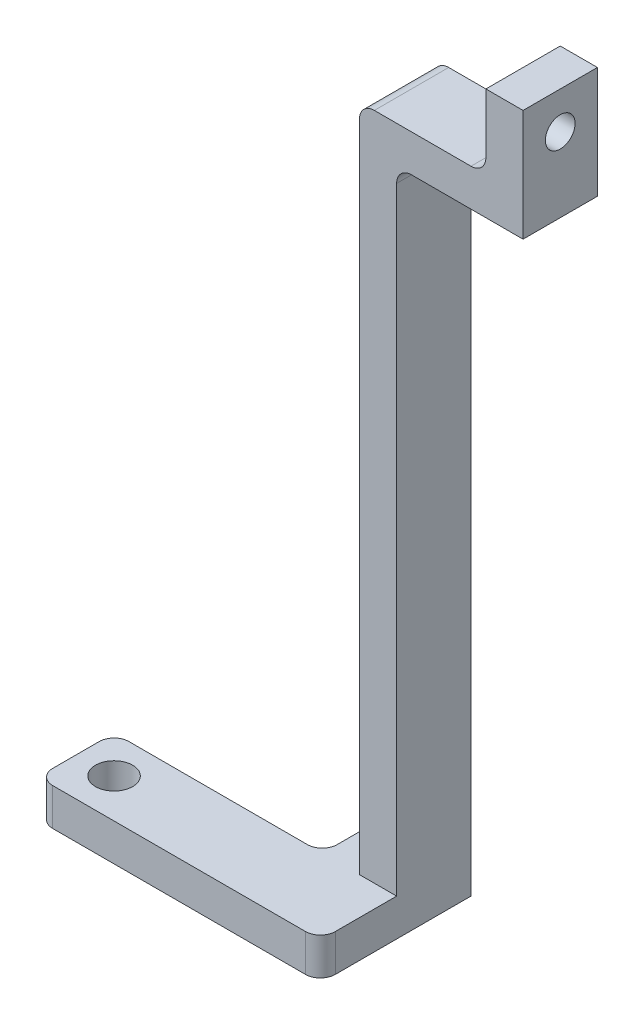
SolidWorks part; units mm, degrees
ref_plane "Front Plane" through (0, 0, 0) normal (0, 0, 1) x (1, 0, 0)
ref_plane "Top Plane" through (0, 0, 0) normal (0, 1, 0) x (1, 0, 0)
ref_plane "Right Plane" through (0, 0, 0) normal (1, 0, 0) x (0, 0, -1)
sketch "Sketch1" plane through (0, 0, 0) normal (0, 1, 0) x (1, 0, 0)
  line L0 (-8, 56.9408) -> (-8, 59.7408)
  line L1 (0, 57.5) -> (0, -57.5) construction
  line L2 (8, 56.9408) -> (8, 59.7408)
  line L3 (-6, 61.7408) -> (6, 61.7408)
  line L4 (39.4147, 47.8999) -> (47.8999, 39.4147)
  line L9 (34.6063, 45.9201) -> (36.5862, 47.8999)
  line L10 (45.9201, 34.6063) -> (47.8999, 36.5862)
  line L15 (61.7408, 6) -> (61.7408, -6)
  line L16 (56.9408, 8) -> (59.7408, 8)
  line L17 (56.9408, -8) -> (59.7408, -8)
  line L22 (47.8999, -39.4147) -> (39.4147, -47.8999)
  line L23 (45.9201, -34.6063) -> (47.8999, -36.5862)
  line L24 (34.6063, -45.9201) -> (36.5862, -47.8999)
  line L29 (6, -61.7408) -> (-6, -61.7408)
  line L30 (8, -56.9408) -> (8, -59.7408)
  line L31 (-8, -56.9408) -> (-8, -59.7408)
  line L36 (-39.4147, -47.8999) -> (-47.8999, -39.4147)
  line L37 (-34.6063, -45.9201) -> (-36.5862, -47.8999)
  line L38 (-45.9201, -34.6063) -> (-47.8999, -36.5862)
  line L43 (-61.7408, -6) -> (-61.7408, 6)
  line L44 (-56.9408, -8) -> (-59.7408, -8)
  line L45 (-56.9408, 8) -> (-59.7408, 8)
  line L50 (-47.8999, 39.4147) -> (-39.4147, 47.8999)
  line L51 (-45.9201, 34.6063) -> (-47.8999, 36.5862)
  line L52 (-34.6063, 45.9201) -> (-36.5862, 47.8999)
  arc A0 (-8, 56.9408) -> (-34.6063, 45.9201) centre (0, 0) ccw
  arc A1 (6, 61.7408) -> (8, 59.7408) centre (6, 59.7408) cw
  arc A2 (-6, 61.7408) -> (-8, 59.7408) centre (-6, 59.7408) ccw
  arc A3 (39.4147, 47.8999) -> (36.5862, 47.8999) centre (38.0005, 46.4857) ccw
  arc A4 (47.8999, 39.4147) -> (47.8999, 36.5862) centre (46.4857, 38.0005) cw
  arc A5 (61.7408, 6) -> (59.7408, 8) centre (59.7408, 6) ccw
  arc A6 (61.7408, -6) -> (59.7408, -8) centre (59.7408, -6) cw
  arc A7 (47.8999, -39.4147) -> (47.8999, -36.5862) centre (46.4857, -38.0005) ccw
  arc A8 (39.4147, -47.8999) -> (36.5862, -47.8999) centre (38.0005, -46.4857) cw
  arc A9 (6, -61.7408) -> (8, -59.7408) centre (6, -59.7408) ccw
  arc A10 (-6, -61.7408) -> (-8, -59.7408) centre (-6, -59.7408) cw
  arc A11 (-39.4147, -47.8999) -> (-36.5862, -47.8999) centre (-38.0005, -46.4857) ccw
  arc A12 (-47.8999, -39.4147) -> (-47.8999, -36.5862) centre (-46.4857, -38.0005) cw
  arc A13 (-61.7408, -6) -> (-59.7408, -8) centre (-59.7408, -6) ccw
  arc A14 (-61.7408, 6) -> (-59.7408, 8) centre (-59.7408, 6) cw
  arc A15 (-47.8999, 39.4147) -> (-47.8999, 36.5862) centre (-46.4857, 38.0005) ccw
  arc A16 (-39.4147, 47.8999) -> (-36.5862, 47.8999) centre (-38.0005, 46.4857) cw
  arc A17 (-45.9201, 34.6063) -> (-56.9408, 8) centre (0, 0) ccw
  arc A18 (-56.9408, -8) -> (-45.9201, -34.6063) centre (0, 0) ccw
  arc A19 (34.6063, 45.9201) -> (8, 56.9408) centre (0, 0) ccw
  arc A20 (-34.6063, -45.9201) -> (-8, -56.9408) centre (0, 0) ccw
  arc A21 (8, -56.9408) -> (34.6063, -45.9201) centre (0, 0) ccw
  arc A22 (45.9201, -34.6063) -> (56.9408, -8) centre (0, 0) ccw
  arc A23 (56.9408, 8) -> (45.9201, 34.6063) centre (0, 0) ccw
  point P11 (8, 61.7408)
  point P14 (-8, 61.7408)
  point P17 (-8, 58.3408)
  point P98 (0, 0)
  dimension "D1" = 115
  dimension "D2" = 2
  dimension "D3" = 16
  dimension "D4" = 2.8
  dimension "D7" = 8
extrude "Boss-Extrude1" add sketch "Sketch1" along normal blind 7
sketch "Sketch2" plane through (0, 7, 0) normal (0, 1, 0) x (1, 0, 0)
  line L0 (-57.5, 0) -> (57.5, 0) construction
  line L1 (0, 0) -> (0, 10) construction
  line L7 (17, 5) -> (22, 5)
  line L14 (0, 10) -> (29.7122, 10) construction
  line L15 (0, 10) -> (-19.5, 10) construction
  line L17 (17, 5) -> (17, 15)
  line L18 (-22, 15) -> (-17, 15)
  line L19 (-22, 15) -> (-22, 5)
  line L20 (-22, 5) -> (-17, 5)
  line L21 (-17, 15) -> (-17, 5)
  line L22 (-22, 15) -> (-17, 5) construction
  line L23 (-22, 5) -> (-17, 15) construction
  line L24 (17, 15) -> (22, 15)
  line L25 (22, 5) -> (22, 15)
  line L26 (17, 5) -> (22, 15) construction
  line L27 (17, 15) -> (22, 5) construction
  circle A0 centre (0, 0) radius 57.5 construction
  point P8 (19.5, 10)
  dimension "D1" = 10
  dimension "D2" = 17
  dimension "D3" = 17
  dimension "D4" = 10
  dimension "D5" = 5
  dimension "D6" = 10
  dimension "D7" = 5
extrude "Boss-Extrude2" add sketch "Sketch2" along normal blind 95
sketch "Sketch15" plane through (0, 0, 0) normal (0, -1, 0) x (1, 0, 0)
  circle A0 centre (0, 0) radius 3.5
  dimension "D1" = 7
extrude "Cut-Extrude3" cut sketch "Sketch15" along direction (0, 1, 0) on the side against the normal up to surface (7 mm away) contours A0 up to face at (0, 7, 0)
sketch "Sketch16" plane through (0, 0, 0) normal (0, -1, 0) x (1, 0, 0)
  line L1 (-6, 59.8) -> (6, 59.8)
  line L2 (-6, 59.8) -> (-6, 57.5)
  line L3 (-6, 57.5) -> (6, 57.5)
  line L4 (6, 59.8) -> (6, 57.5)
  point P5 (0, 57.5)
  dimension "D1" = 2.3
  dimension "D2" = 12
  dimension "D3" = 57.5
sketch "Sketch17" plane through (0, 7, 0) normal (0, 1, 0) x (1, 0, 0)
  line L0 (-6, -57.5) -> (6, -57.5) construction
  line L1 (-6, -57.5) -> (6, -57.5)
  line L2 (-6, -57.5) -> (-6, -60.5)
  line L3 (-6, -60.5) -> (6, -60.5)
  line L4 (6, -60.5) -> (6, -57.5)
  dimension "D1" = 3
ref_axis "Axis1" through (0, 107.1, 0) along (0, -1, 0)
loft "Cut-Loft2" cut profiles "Sketch16", "Sketch17" connector at (6, 0, 59.8) connector at (6, 7, 60.5)
pattern_circular "CirPattern1" count 8 over 360 about axis through (0, 107.1, 0) along (0, -1, 0) of "Cut-Loft2"
sketch "Sketch18" plane through (-17, 0, 0) normal (1, 0, 0) x (0, 0, -1)
  line L0 (15, 102) -> (15, 7) construction
  line L1 (5, 102) -> (15, 102)
  line L2 (5, 102) -> (5, 97)
  line L3 (5, 97) -> (15, 97)
  line L4 (15, 102) -> (15, 97)
  dimension "D1" = 5
extrude "Boss-Extrude3" add sketch "Sketch18" along normal up to surface (34 mm away) up to face at (17, 54.5, -10)
sketch "Sketch19" plane through (0, 0, -15) normal (0, 0, -1) x (-1, 0, 0)
  line L0 (-17, 93) -> (-11.0447, 92.2688)
  line L1 (-17, 97) -> (-17, 7) construction
  line L4 (-11, 91) -> (-19.8185, 91) construction
  line L5 (-17, 89) -> (-11.0447, 89.7312)
  line L6 (-17, 93) -> (-17, 89)
  arc A1 (-11.0447, 92.2688) -> (-11.0447, 89.7312) centre (-11.2005, 91) cw
  dimension "D1" = 6
  dimension "D4" = 4
  dimension "D2" = 7
  dimension "D3" = 4
extrude "Boss-Extrude4" add sketch "Sketch19" against normal blind 10
fillet "Fillet1" radius 2 2 edges at (17, 93, -10) (17, 89, -10)
fillet "Fillet2" radius 2 4 edges at (-22, 102, -10) (22, 102, -10) (-17, 97, -10) (17, 97, -10)
pattern_linear "LPattern2" count 10 spacing 8 along (0, -1, 0) of "Fillet1", "Boss-Extrude4"
sketch "Sketch20" plane through (0, 7, 0) normal (0, 1, 0) x (1, 0, 0)
  line L0 (0, 0) -> (0, 50) construction
  circle A0 centre (0, 50) radius 2.5
  dimension "D2" = 5
  dimension "D1" = 50
extrude "Cut-Extrude4" cut sketch "Sketch20" against normal blind 10
pattern_circular "CirPattern2" count 4 over 360 about axis through (0, 107.1, 0) along (0, -1, 0) of "Cut-Extrude4"
sketch "Sketch21" plane through (0, 0, 0) normal (1, 0, 0) x (0, 0, -1)
  line L1 (67.451, 109.7761) -> (-68.4979, 109.7761)
  line L2 (67.451, 109.7761) -> (67.451, 0)
  line L3 (67.451, 0) -> (-68.4979, 0)
  line L4 (-68.4979, 109.7761) -> (-68.4979, 0)
  dimension "D1" = 109.7761
  dimension "D2" = 135.9489
  dimension "D3" = 68.4979
extrude "Cut-Extrude5" cut sketch "Sketch21" along normal up to surface (61.7408 mm away) up to face at (61.7408, 3.5, 0)
sketch "Sketch22" plane through (0, 7, 0) normal (0, 1, 0) x (1, 0, 0)
  line L1 (-17, 5) -> (-53, 5)
  line L2 (-17, 5) -> (-17, -3.2506)
  line L3 (-19, -5.2506) -> (-53, -5.2506)
  line L4 (-55, 3) -> (-55, -3.2506)
  circle A0 centre (-50, 0) radius 2.5 construction
  circle A1 centre (-50, 0) radius 2.5
  arc A2 (-19, -5.2506) -> (-17, -3.2506) centre (-19, -3.2506) ccw
  arc A3 (-55, 3) -> (-53, 5) centre (-53, 3) cw
  arc A4 (-53, -5.2506) -> (-55, -3.2506) centre (-53, -3.2506) cw
  point P10 (-17, -5.2506)
  point P15 (-55, -5.2506)
  dimension "D3" = 2
  dimension "D1" = 38
  dimension "D2" = 10.2506
extrude "Boss-Extrude5" add sketch "Sketch22" along normal blind 5
sketch "Sketch23" plane through (0, 7, 0) normal (0, 1, 0) x (1, 0, 0)
  line L25 (0, 60.5) -> (0, 61.7408)
  line L26 (0, 61.7408) -> (-6, 61.7408)
  line L27 (-8, 59.7408) -> (-8, 56.9408)
  line L28 (-34.6063, 45.9201) -> (-36.5862, 47.8999)
  line L29 (-39.4147, 47.8999) -> (-47.8999, 39.4147)
  line L30 (-47.8999, 36.5862) -> (-45.9201, 34.6063)
  line L31 (-56.9408, 8) -> (-59.7408, 8)
  line L32 (-61.7408, 6) -> (-61.7408, -6)
  line L33 (-59.7408, -8) -> (-56.9408, -8)
  line L34 (-45.9201, -34.6063) -> (-47.8999, -36.5862)
  line L35 (-47.8999, -39.4147) -> (-39.4147, -47.8999)
  line L36 (-36.5862, -47.8999) -> (-34.6063, -45.9201)
  line L37 (-8, -56.9408) -> (-8, -59.7408)
  line L38 (-6, -61.7408) -> (0, -61.7408)
  line L39 (0, -61.7408) -> (0, -60.5)
  line L40 (0, -60.5) -> (-6, -60.5)
  line L41 (-6, -60.5) -> (-6, -57.5)
  line L42 (-6, -57.5) -> (0, -57.5)
  line L43 (0, -57.5) -> (0, -52.5)
  line L44 (0, -47.5) -> (0, -3.5)
  line L45 (0, 3.5) -> (0, 47.5)
  line L46 (0, 52.5) -> (0, 57.5)
  line L47 (0, 57.5) -> (-6, 57.5)
  line L48 (-6, 57.5) -> (-6, 60.5)
  line L49 (-6, 60.5) -> (0, 60.5)
  line L50 (0, 60.5) -> (0, 61.7408)
  line L51 (0, 61.7408) -> (-6, 61.7408)
  line L52 (-8, 59.7408) -> (-8, 56.9408)
  line L53 (-34.6063, 45.9201) -> (-36.5862, 47.8999)
  line L54 (-39.4147, 47.8999) -> (-47.8999, 39.4147)
  line L55 (-47.8999, 36.5862) -> (-45.9201, 34.6063)
  line L56 (-56.9408, 8) -> (-59.7408, 8)
  line L57 (-61.7408, 6) -> (-61.7408, -6)
  line L58 (-59.7408, -8) -> (-56.9408, -8)
  line L59 (-45.9201, -34.6063) -> (-47.8999, -36.5862)
  line L60 (-47.8999, -39.4147) -> (-39.4147, -47.8999)
  line L61 (-36.5862, -47.8999) -> (-34.6063, -45.9201)
  line L62 (-8, -56.9408) -> (-8, -59.7408)
  line L63 (-6, -61.7408) -> (0, -61.7408)
  line L64 (0, -61.7408) -> (0, -60.5)
  line L65 (0, -60.5) -> (-6, -60.5)
  line L66 (-6, -60.5) -> (-6, -57.5)
  line L67 (-6, -57.5) -> (0, -57.5)
  line L68 (0, -57.5) -> (0, -52.5)
  line L69 (0, -47.5) -> (0, -3.5)
  line L70 (0, 3.5) -> (0, 47.5)
  line L71 (0, 52.5) -> (0, 57.5)
  line L72 (0, 57.5) -> (-6, 57.5)
  line L73 (-6, 57.5) -> (-6, 60.5)
  line L74 (-6, 60.5) -> (0, 60.5)
  arc A15 (-6, 61.7408) -> (-8, 59.7408) centre (-6, 59.7408) ccw
  arc A16 (-8, 56.9408) -> (-34.6063, 45.9201) centre (0, 0) ccw
  arc A17 (-36.5862, 47.8999) -> (-39.4147, 47.8999) centre (-38.0005, 46.4857) ccw
  arc A18 (-47.8999, 39.4147) -> (-47.8999, 36.5862) centre (-46.4857, 38.0005) ccw
  arc A19 (-45.9201, 34.6063) -> (-56.9408, 8) centre (0, 0) ccw
  arc A20 (-59.7408, 8) -> (-61.7408, 6) centre (-59.7408, 6) ccw
  arc A21 (-61.7408, -6) -> (-59.7408, -8) centre (-59.7408, -6) ccw
  arc A22 (-56.9408, -8) -> (-45.9201, -34.6063) centre (0, 0) ccw
  arc A23 (-47.8999, -36.5862) -> (-47.8999, -39.4147) centre (-46.4857, -38.0005) ccw
  arc A24 (-39.4147, -47.8999) -> (-36.5862, -47.8999) centre (-38.0005, -46.4857) ccw
  arc A25 (-34.6063, -45.9201) -> (-8, -56.9408) centre (0, 0) ccw
  arc A26 (-8, -59.7408) -> (-6, -61.7408) centre (-6, -59.7408) ccw
  arc A27 (0, -47.5) -> (0, -52.5) centre (0, -50) ccw
  arc A28 (0, 3.5) -> (0, -3.5) centre (0, 0) ccw
  arc A29 (0, 52.5) -> (0, 47.5) centre (0, 50) ccw
  arc A30 (-6, 61.7408) -> (-8, 59.7408) centre (-6, 59.7408) ccw
  arc A31 (-8, 56.9408) -> (-34.6063, 45.9201) centre (0, 0) ccw
  arc A32 (-36.5862, 47.8999) -> (-39.4147, 47.8999) centre (-38.0005, 46.4857) ccw
  arc A33 (-47.8999, 39.4147) -> (-47.8999, 36.5862) centre (-46.4857, 38.0005) ccw
  arc A34 (-45.9201, 34.6063) -> (-56.9408, 8) centre (0, 0) ccw
  arc A35 (-59.7408, 8) -> (-61.7408, 6) centre (-59.7408, 6) ccw
  arc A36 (-61.7408, -6) -> (-59.7408, -8) centre (-59.7408, -6) ccw
  arc A37 (-56.9408, -8) -> (-45.9201, -34.6063) centre (0, 0) ccw
  arc A38 (-47.8999, -36.5862) -> (-47.8999, -39.4147) centre (-46.4857, -38.0005) ccw
  arc A39 (-39.4147, -47.8999) -> (-36.5862, -47.8999) centre (-38.0005, -46.4857) ccw
  arc A40 (-34.6063, -45.9201) -> (-8, -56.9408) centre (0, 0) ccw
  arc A41 (-8, -59.7408) -> (-6, -61.7408) centre (-6, -59.7408) ccw
  arc A42 (0, -47.5) -> (0, -52.5) centre (0, -50) ccw
  arc A43 (0, 3.5) -> (0, -3.5) centre (0, 0) ccw
  arc A44 (0, 52.5) -> (0, 47.5) centre (0, 50) ccw
  dimension "D1" = 0
extrude "Cut-Extrude6" cut sketch "Sketch23" against normal blind 10
sketch "Sketch24" plane through (0, 0, 60.5) normal (0, 0, 1) x (1, 0, 0)
  line L4 (0, 0) -> (0, 7)
  line L5 (0, 7) -> (-6, 7)
  line L6 (-6, 7) -> (-6, 0)
  line L7 (-6, 0) -> (0, 0)
  line L8 (0, 0) -> (0, 7)
  line L9 (0, 7) -> (-6, 7)
  line L10 (-6, 7) -> (-6, 0)
  line L11 (-6, 0) -> (0, 0)
  dimension "D1" = 0
extrude "Cut-Extrude7" cut sketch "Sketch24" against normal blind 1
sketch "Sketch25" plane through (0, 0, -60.5) normal (0, 0, -1) x (-1, 0, 0)
  line L4 (6, 0) -> (6, 7)
  line L5 (6, 7) -> (0, 7)
  line L6 (0, 7) -> (0, 0)
  line L7 (0, 0) -> (6, 0)
  line L8 (6, 0) -> (6, 7)
  line L9 (6, 7) -> (0, 7)
  line L10 (0, 7) -> (0, 0)
  line L11 (0, 0) -> (6, 0)
  dimension "D1" = 0
extrude "Cut-Extrude8" cut sketch "Sketch25" against normal blind 1
sketch "Sketch26" plane through (-22, 0, 0) normal (-1, 0, 0) x (0, 0, 1)
  line L0 (-15, 100) -> (-15, 7) construction
  line L1 (-5, 7) -> (-15, 7)
  line L2 (-5, 7) -> (-5, 12)
  line L3 (-5, 12) -> (-15, 12)
  line L4 (-15, 7) -> (-15, 12)
extrude "Boss-Extrude6" add sketch "Sketch26" along normal blind 5
sketch "Sketch27" plane through (0, 102, 0) normal (0, 1, 0) x (1, 0, 0)
  line L0 (0, 15) -> (-20, 15) construction
  line L1 (0, 5) -> (-5, 5)
  line L2 (0, 5) -> (0, 15)
  line L3 (0, 15) -> (-5, 15)
  line L4 (-5, 5) -> (-5, 15)
  dimension "D1" = 5
extrude "Boss-Extrude7" add sketch "Sketch27" along normal blind 10
sketch "Sketch29" plane through (-5, 0, 0) normal (-1, 0, 0) x (0, 0, 1)
  line L0 (-5, 112) -> (-15, 102) construction
  circle A0 centre (-10, 107) radius 2
  dimension "D1" = 4
extrude "Cut-Extrude9" cut sketch "Sketch29" against normal up to surface (5 mm away) up to face at (0, 104.5, -10)
fillet "Fillet3" radius 2 3 edges at (-27, 9.5, -5) (-5, 102, -10) (-27, 9.5, -15)
equation "\"85.00.00mm\"=8500"
